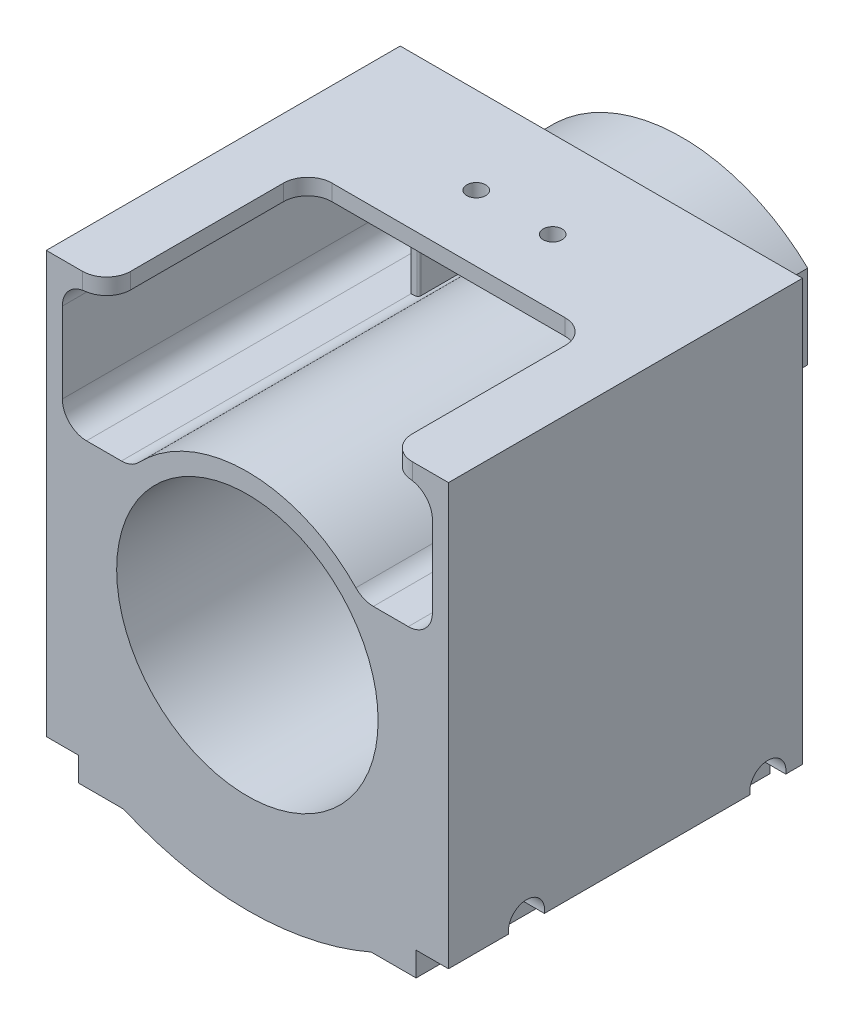
SolidWorks part; units mm, degrees
ref_plane "Front Plane" through (0, 0, 0) normal (0, 0, 1) x (1, 0, 0)
ref_plane "Top Plane" through (0, 0, 0) normal (0, 1, 0) x (1, 0, 0)
ref_plane "Right Plane" through (0, 0, 0) normal (1, 0, 0) x (0, 0, -1)
sketch "Sketch1" plane through (0, 0, 0) normal (0, 0, 1) x (1, 0, 0)
  line L1 (0, 0) -> (0, -38.55) construction
  line L2 (-25, 0) -> (-25, -29.3445)
  line L3 (25, 0) -> (25, -29.3445)
  line L4 (-25, 0) -> (-25, 20)
  line L5 (-25, 20) -> (25, 20)
  line L6 (25, 20) -> (25, 0)
  line L7 (25, -29.3445) -> (25, -32.3445)
  line L8 (25, -32.3445) -> (20.9746, -32.3445)
  line L9 (20.9746, -32.3445) -> (20.9746, -35.3445)
  line L10 (20.9746, -35.3445) -> (15.3904, -35.3445)
  line L11 (-20.9746, -35.3445) -> (-15.3904, -35.3445)
  line L12 (-20.9746, -32.3445) -> (-20.9746, -35.3445)
  line L13 (-25, -32.3445) -> (-20.9746, -32.3445)
  line L14 (-25, -29.3445) -> (-25, -32.3445)
  arc A0 (-25, -29.3445) -> (-20.9746, -32.3445) centre (0, 0) ccw construction
  arc A1 (20.9746, -32.3445) -> (25, -29.3445) centre (0, 0) ccw construction
  arc A2 (15.3904, -35.3445) -> (20.9746, -32.3445) centre (0, 0) ccw construction
  arc A3 (-15.3904, -35.3445) -> (15.3904, -35.3445) centre (0, 0) ccw
  arc A4 (-20.9746, -32.3445) -> (-15.3904, -35.3445) centre (0, 0) ccw construction
  dimension "D1" = 77.1
  dimension "D2" = 50
  dimension "D3" = 20
  dimension "D4" = 3
  dimension "D5" = 3
extrude "Boss-Extrude2" add sketch "Sketch1" along normal blind 44 from offset 6
sketch "Sketch2" plane through (0, 0, 50) normal (0, 0, 1) x (1, 0, 0)
  line L6 (0, 6.25) -> (0, -26.25) construction
  circle A0 centre (0, -10) radius 16.25
  dimension "D2" = 32.5
  dimension "D1" = 10
extrude "Cut-Extrude1" cut sketch "Sketch2" against normal through all both
sketch "Sketch4" plane through (0, 0, 50) normal (0, 0, 1) x (1, 0, 0)
  line L0 (-23, 18) -> (23, 18)
  line L3 (0, 20) -> (0, 6.25) construction
  line L4 (25, 20) -> (-25, 20) construction
  line L5 (23, 2) -> (14.3178, 2)
  line L6 (-23, 18) -> (-23, 2)
  line L7 (-23, 2) -> (-14.3178, 2)
  line L8 (-25, 20) -> (-25, -32.3445) construction
  line L9 (23, 18) -> (23, 2)
  circle A2 centre (0, -10) radius 16.25 construction
  arc A3 (14.3178, 2) -> (-14.3178, 2) centre (0, -10) ccw
  point P2 (0, 13.125)
  point P14 (0, 18)
  dimension "D1" = 37.3631
  dimension "D2" = 2
  dimension "D3" = 2
  dimension "D4" = 16
extrude "Cut-Extrude3" cut sketch "Sketch4" against normal through all
fillet "Fillet1" radius 3 6 edges at (23, 18, 28) (23, 2, 28) (14.3178, 2, 28) (-14.3178, 2, 28) (-23, 2, 28) (-23, 18, 28)
sketch "Sketch5" plane through (0, 20, 0) normal (0, 1, 0) x (1, 0, 0)
  line L0 (25, -50) -> (-25, -50) construction
  line L1 (-17.5, -50) -> (17.5, -50)
  line L2 (-17.5, -50) -> (-17.5, -25)
  line L3 (-17.5, -25) -> (17.5, -25)
  line L4 (17.5, -50) -> (17.5, -25)
  line L5 (0, 0) -> (0, -50) construction
  dimension "D1" = 35
  dimension "D2" = 25
extrude "Cut-Extrude4" cut sketch "Sketch5" against normal blind 10
fillet "Fillet2" radius 3 4 edges at (17.5, 19, 50) (17.5, 19, 25) (-17.5, 19, 25) (-17.5, 19, 50)
ref_plane "Plane1" through (0, 0, 14) normal (0, 0, 1) x (1, 0, 0)
sketch "Sketch6" plane through (0, 0, 14) normal (0, 0, 1) x (1, 0, 0)
  line L0 (0, -10) -> (0, 3) construction
  line L1 (0, -10) -> (4.4463, 2.216) construction
  circle A1 centre (0, -10) radius 16.25 construction
  circle A3 centre (0, -10) radius 9.5
  circle A8 centre (0, -10) radius 16.25
  circle A9 centre (0, -10) radius 13 construction
  circle A10 centre (4.4463, 2.216) radius 1.65
  circle A11 centre (12.216, -14.4463) radius 1.65
  circle A12 centre (-4.4463, -22.216) radius 1.65
  circle A13 centre (-12.216, -5.5537) radius 1.65
  dimension "D1" = 19
  dimension "D6" = 13
  dimension "D2" = 3.5
  dimension "D3" = 3.3
  dimension "D4" = 20
  dimension "D5" = 4
extrude "Boss-Extrude3" add sketch "Sketch6" against normal blind 5
sketch "Sketch7" plane through (0, 0, 0) normal (1, 0, 0) x (0, 0, -1)
  circle A0 centre (-40.3, -32) radius 2.25
  circle A1 centre (-10.3, -32) radius 2.25
  dimension "D3" = 4.5
  dimension "D1" = 32
  dimension "D2" = 10.3
  dimension "D4" = 30
extrude "Cut-Extrude5" cut sketch "Sketch7" against normal through all both and the other way through all
sketch "Sketch8" plane through (0, 20, 0) normal (0, 1, 0) x (1, 0, 0)
  line L0 (0, -6) -> (0, -25) construction
  line L1 (25, -6) -> (-25, -6) construction
  line L2 (14.5, -25) -> (-14.5, -25) construction
  circle A0 centre (-4.75, -16.8) radius 1.175
  circle A1 centre (4.75, -16.8) radius 1.175
  dimension "D1" = 2.35
  dimension "D2" = 9.5
  dimension "D3" = 10.8
extrude "Cut-Extrude6" cut sketch "Sketch8" against normal up to next contours A0 | A1
sketch "Sketch9" plane through (0, 0, 50) normal (0, 0, 1) x (1, 0, 0)
  line L0 (0, -28.5) -> (0, -5) construction
  line L1 (0, -10) -> (0, -28.5) construction
  line L2 (-15.6553, 2) -> (-15.6553, 11.4123)
  line L3 (15.6553, 2) -> (15.6553, 11.4123)
  line L4 (0, 8.6815) -> (0, 17.6815) construction
  line L5 (-14.6553, 2.1716) -> (-14.6553, 10.5325)
  line L6 (14.6553, 2.1716) -> (14.6553, 10.5325)
  line L7 (-15.6553, 2) -> (-15.6553, 1)
  line L8 (15.6553, 2) -> (15.6553, 1)
  line L9 (14.6553, 2) -> (14.6553, 10.9784) construction
  line L10 (-14.6553, 2) -> (-14.6553, 10.9784) construction
  arc A0 (13.4892, 2.9245) -> (-13.4892, 2.9245) centre (0, -10) ccw construction
  arc A1 (13.4892, 2.9245) -> (-13.4892, 2.9245) centre (0, -10) ccw
  arc A3 (-15.6553, 11.4123) -> (15.6553, 11.4123) centre (0, -5) cw
  arc A4 (13.4892, 2.9245) -> (15.6553, 2) centre (15.6553, 5) ccw construction
  arc A5 (-15.6553, 2) -> (-13.4892, 2.9245) centre (-15.6553, 5) ccw construction
  arc A6 (13.4892, 2.9245) -> (15.6553, 2) centre (15.6553, 5) ccw
  arc A7 (-15.6553, 2) -> (-13.4892, 2.9245) centre (-15.6553, 5) ccw
  arc A8 (12.7671, 2.2327) -> (15.6553, 1) centre (15.6553, 5) ccw
  arc A9 (12.7671, 2.2327) -> (-12.7671, 2.2327) centre (0, -10) ccw
  arc A10 (-15.6553, 1) -> (-12.7671, 2.2327) centre (-15.6553, 5) ccw
  arc A11 (-14.3156, 11.2835) -> (14.3156, 11.2835) centre (0, -5) cw
  arc A12 (-14.6553, 10.9784) -> (14.6553, 10.9784) centre (0, -5) cw construction
  arc A13 (14.6553, 10.5325) -> (14.3156, 11.2835) centre (13.6553, 10.5325) ccw
  arc A14 (-14.6553, 10.5325) -> (-14.3156, 11.2835) centre (-13.6553, 10.5325) cw
  dimension "D1" = 9
  dimension "D2" = 1
  dimension "D4" = 1
  dimension "Ring Gear Outer Dia to Center" = 23.5
  dimension "Pinion to Ring Gear Outer Diameter" = 18.5
  dimension "D3" = 1
extrude "Boss-Extrude4" add sketch "Sketch9" along normal blind 8 and the other way blind 10 from surface contours L5 A11 L6 L2 L3 A3 A6 | L7 A10 A9 A8 L8 L2 L3 A6 region at (-15.0935, 1.7255, 50) region at (-15.3051, 6.7061, 50) starting at face at (0, 7.9303, 6)
fillet "Fillet5" radius 0.25 8 edges at (14.0281, 2.4797, -4) (-14.0281, 2.4797, -4) (14.6553, 6.352, -4) (14.5664, 10.9446, -4) (-14.6553, 6.352, -4) (-14.5664, 10.9446, -4) (0, 8.6815, -4) (0, 16.6815, -4)
fillet "Fillet6" radius 0.25 5 edges at (14.6553, 6.352, 14) (14.5664, 10.9446, 14) (-14.6553, 6.352, 14) (-14.5664, 10.9446, 14) (0, 16.6815, 14)
